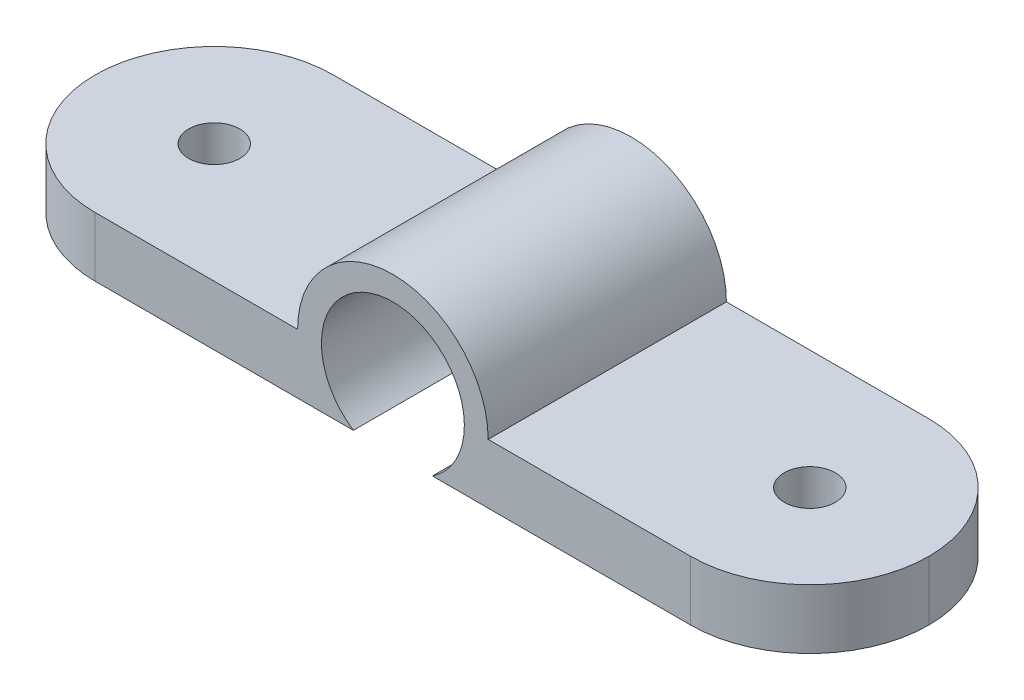
SolidWorks part; units mm, degrees
ref_plane "Front Plane" through (0, 0, 0) normal (0, 0, 1) x (1, 0, 0)
ref_plane "Top Plane" through (0, 0, 0) normal (0, 1, 0) x (1, 0, 0)
ref_plane "Right Plane" through (0, 0, 0) normal (1, 0, 0) x (0, 0, -1)
sketch "Sketch1" plane through (0, 0, 0) normal (0, 1, 0) x (1, 0, 0)
  line L0 (-57.2399, 20) -> (12.7601, 20)
  line L1 (12.7601, 20) -> (12.7601, 0)
  line L2 (12.7601, 0) -> (-57.2399, 0)
  line L3 (-57.2399, 0) -> (-57.2399, 20)
  dimension "D1" = 20
  dimension "D2" = 70
extrude "Boss-Extrude1" add sketch "Sketch1" along normal blind 5
fillet "Fillet1" radius 10 4 edges at (12.7601, 2.5, 0) (12.7601, 2.5, -20) (-57.2399, 2.5, 0) (-57.2399, 2.5, -20)
sketch "Sketch2" plane through (0, 5, 0) normal (0, 1, 0) x (1, 0, 0)
  circle A0 centre (-47.2399, 10) radius 2.15
  circle A1 centre (2.7601, 10) radius 2.15
  dimension "D1" = 4.3
  dimension "D2" = 4.3
extrude "Cut-Extrude1" cut sketch "Sketch2" against normal blind 10
sketch "Sketch3" plane through (0, 0, -20) normal (0, 0, -1) x (-1, 0, 0)
  line L0 (-2.7601, 5) -> (47.2399, 5) construction
  line L1 (14.2399, 5) -> (30.2399, 5)
  arc A0 (14.2399, 5) -> (30.2399, 5) centre (22.2399, 5) cw
  dimension "D1" = 8
extrude "Boss-Extrude2" add sketch "Sketch3" against normal blind 20
sketch "Sketch6" plane through (0, 0, -20) normal (0, 0, -1) x (-1, 0, 0)
  circle A0 centre (22.2399, 5) radius 6
  dimension "D1" = 12
extrude "Cut-Extrude3" cut sketch "Sketch6" against normal blind 20
